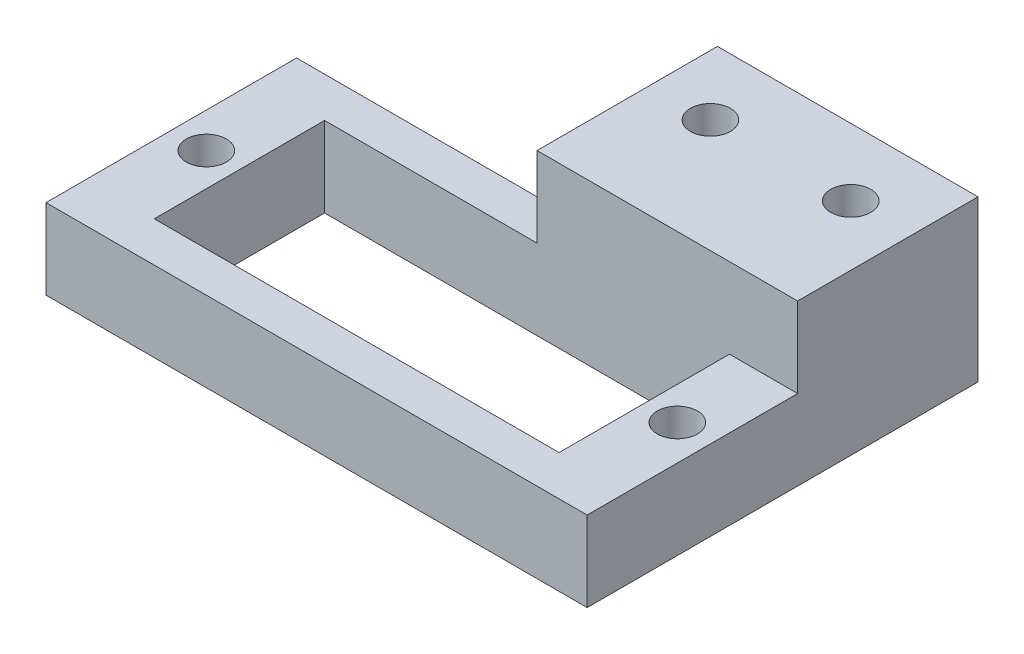
SolidWorks part; units mm, degrees
ref_plane "Płaszczyzna przednia" through (0, 0, 0) normal (0, 0, 1) x (1, 0, 0)
ref_plane "Płaszczyzna górna" through (0, 0, 0) normal (0, 1, 0) x (1, 0, 0)
ref_plane "Płaszczyzna prawa" through (0, 0, 0) normal (1, 0, 0) x (0, 0, -1)
sketch "Szkic1" plane through (0, 0, 0) normal (0, 1, 0) x (1, 0, 0)
  line L0 (-13.5, 2.75) -> (0.5, 2.75)
  line L1 (13.5, -9.75) -> (-13.5, -9.75)
  line L2 (13.5, -9.75) -> (13.5, 9.75)
  line L3 (13.5, 9.75) -> (0.5, 9.75)
  line L4 (-13.5, -9.75) -> (-13.5, 2.75)
  line L5 (13.5, -9.75) -> (-3.8077, 2.75) construction
  line L6 (13.5, 9.75) -> (-13.5, -9.75) construction
  line L7 (10.1, -7.75) -> (-10.1, -7.75)
  line L8 (10.1, -7.75) -> (10.1, 0.75)
  line L9 (10.1, 0.75) -> (-10.1, 0.75)
  line L10 (-10.1, -7.75) -> (-10.1, 0.75)
  line L11 (10.1, -7.75) -> (-10.1, 0.75) construction
  line L12 (10.1, 0.75) -> (-10.1, -7.75) construction
  line L13 (0.5, 2.75) -> (0.5, 9.75)
  circle A0 centre (11.75, -3.5) radius 1
  circle A1 centre (-11.75, -3.5) radius 1
  circle A2 centre (3.5, 6.4) radius 1
  circle A3 centre (10.5, 6.4) radius 1
  point P0 (0, 0)
  point P1 (0, 0)
  point P6 (0, -3.5)
  dimension "D6" = 23.5
  dimension "D8" = 2
  dimension "D9" = 2
  dimension "D10" = 2
  dimension "D13" = 27
  dimension "D2" = 9
  dimension "D3" = 20.2
  dimension "D4" = 8.5
  dimension "D5" = 2
  dimension "D7" = 11.75
  dimension "D11" = 5.65
  dimension "D12" = 3
  dimension "D14" = 7
  dimension "D15" = 13
  dimension "D16" = 2
extrude "Dodanie-wyciągnięcie2" add sketch "Szkic1" along normal blind 4
sketch "Szkic3" plane through (0, 4, 0) normal (0, -1, 0) x (1, 0, 0)
  line L0 (10.1, -0.75) -> (-10.1, -0.75) construction
  line L1 (0.5, -0.75) -> (13.5, -0.75)
  line L2 (0.5, -0.75) -> (0.5, -9.75)
  line L3 (0.5, -9.75) -> (13.5, -9.75)
  line L4 (13.5, -0.75) -> (13.5, -9.75)
  line L5 (13.5, 9.75) -> (13.5, -9.75) construction
  dimension "D1" = 9
  dimension "D2" = 13
extrude "Dodanie-wyciągnięcie3" add sketch "Szkic3" against normal blind 4
extrude "Wytnij-wyciągnięcie2" cut sketch "Szkic1<3>" along normal through all contours A3 | A2 region at (10.5, 0, -6.4)
sketch "Szkic1<3>" plane through (0, 0, 0) normal (0, 1, 0) x (1, 0, 0) same geometry as "Szkic1"
